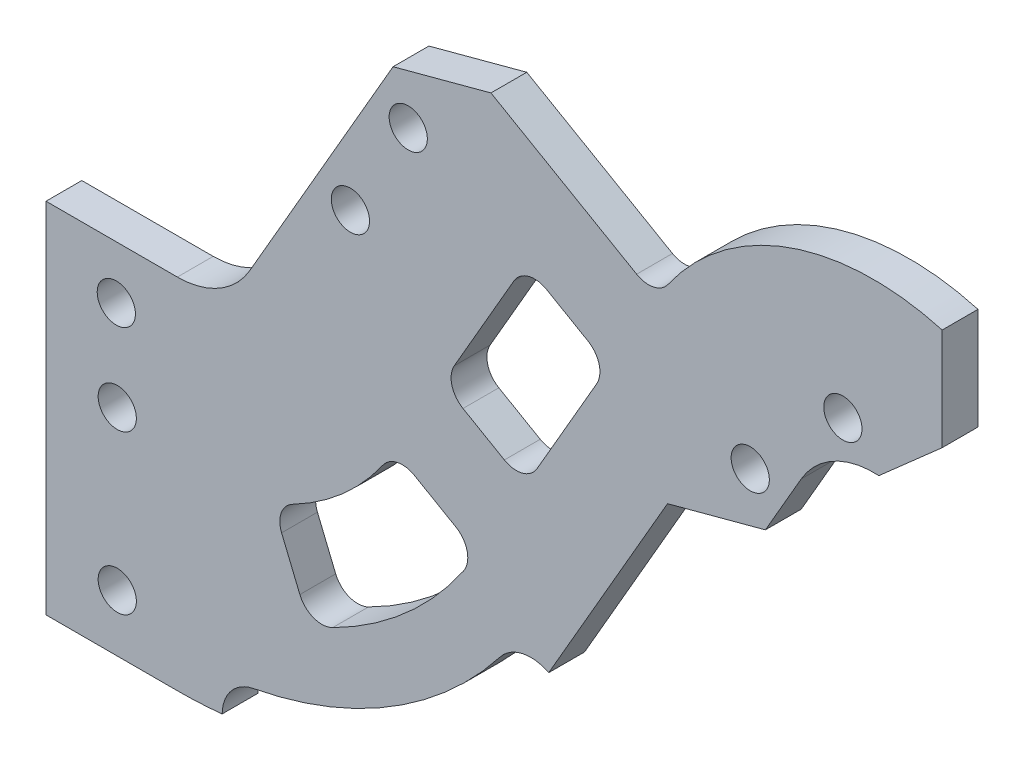
SolidWorks part; units mm, degrees
ref_plane "Front Plane" through (0, 0, 0) normal (0, 0, 1) x (1, 0, 0)
ref_plane "Top Plane" through (0, 0, 0) normal (0, 1, 0) x (1, 0, 0)
ref_plane "Right Plane" through (0, 0, 0) normal (1, 0, 0) x (0, 0, -1)
sketch "Sketch1" plane through (0, 0, 0) normal (0, 0, 1) x (1, 0, 0)
  line L0 (-45.5248, 28.6646) -> (-37.3286, 30.8608) construction
  line L1 (-53.0248, 15.6742) -> (-45.5248, 28.6646) construction
  line L2 (-45.5248, 28.6646) -> (-37.3286, 30.8608)
  line L3 (-57.5248, 7.88) -> (-45.5248, 28.6646)
  line L4 (-30.6183, -5.5166) -> (-22.544, 8.4685) construction
  line L5 (-22.544, 8.4685) -> (-14.3479, 10.6646) construction
  line L6 (-14.3479, 10.6646) -> (-11.3479, 15.8608) construction
  line L7 (-4.8483, 19.3471) -> (0.4544, 24.0249) construction
  line L8 (-32.4942, -8.7657) -> (-22.544, 8.4685)
  line L9 (-22.544, 8.4685) -> (-14.3479, 10.6646)
  line L10 (-14.3479, 10.6646) -> (-11.3479, 15.8608)
  line L11 (-4.8483, 19.3471) -> (0.4544, 24.0249)
  line L12 (0.4544, 24.0249) -> (0.4544, 32.5611)
  line L13 (-63.587, 4.38) -> (-74.587, 4.38)
  line L14 (-74.587, 4.38) -> (-74.587, -25.62)
  line L15 (-74.587, -25.62) -> (-63.587, -25.62)
  line L16 (-63.587, -1.62) -> (-63.587, -25.62) construction
  line L17 (-28.6042, 25.8237) -> (-25.1288, 23.8172) construction
  line L18 (-29.2043, 16.9326) -> (-32.6684, 18.9326) construction
  line L19 (-35.4004, 18.2005) -> (-40.4004, 9.5403) construction
  line L20 (-39.6684, 6.8082) -> (-36.2043, 4.8082) construction
  line L21 (-33.4722, 5.5403) -> (-28.4722, 14.2005) construction
  line L22 (-54.8583, -9.8051) -> (-53.3295, -13.5155) construction
  line L23 (-43.7438, -0.0764) -> (-40.2685, -2.0829) construction
  line L24 (-43.7438, -0.0764) -> (-40.2685, -2.0829)
  line L25 (-54.8583, -9.8051) -> (-53.3295, -13.5155)
  line L26 (-33.4722, 5.5403) -> (-28.4722, 14.2005)
  line L27 (-39.6684, 6.8082) -> (-36.2043, 4.8082)
  line L28 (-35.4004, 18.2005) -> (-40.4004, 9.5403)
  line L29 (-29.2043, 16.9326) -> (-32.6684, 18.9326)
  line L30 (-37.3286, 30.8608) -> (-25.1288, 23.8172)
  arc A2 (-4.8483, 19.3471) -> (-11.3479, 15.8608) centre (-5.2857, 12.3608) ccw construction
  arc A3 (-4.8483, 19.3471) -> (-11.3479, 15.8608) centre (-5.2857, 12.3608) ccw
  arc A4 (-57.5248, 7.88) -> (-63.587, 4.38) centre (-63.587, 11.38) cw
  arc A5 (-57.1936, -22.268) -> (-59.8368, -25.4294) centre (-56.587, -25.4609) ccw
  arc A6 (-32.4942, -8.7657) -> (-36.5568, -9.6541) centre (-33.9919, -11.65) ccw
  arc A7 (-57.1936, -22.268) -> (-36.5568, -9.6541) centre (-63.587, 11.38) ccw
  arc A9 (-63.587, -25.62) -> (-59.8368, -25.4294) centre (-63.587, 11.38) ccw
  arc A10 (-59.7655, -29.4415) -> (-29.1738, -10.9075) centre (-63.587, 11.38) ccw construction
  arc A11 (-63.587, -1.62) -> (-52.3286, 4.88) centre (-63.587, 11.38) ccw construction
  arc A14 (-25.1288, 23.8172) -> (-22.4903, 24.4024) centre (-24.1288, 25.5493) ccw construction
  arc A15 (13.3616, 22.0189) -> (-22.4903, 24.4024) centre (-5.2857, 12.3608) ccw construction
  arc A16 (-32.6684, 18.9326) -> (-35.4004, 18.2005) centre (-33.6684, 17.2005) ccw construction
  arc A17 (-40.4004, 9.5403) -> (-39.6684, 6.8082) centre (-38.6684, 8.5403) ccw construction
  arc A18 (-36.2043, 4.8082) -> (-33.4722, 5.5403) centre (-35.2043, 6.5403) ccw construction
  arc A19 (-28.4722, 14.2005) -> (-29.2043, 16.9326) centre (-30.2043, 15.2005) ccw construction
  arc A20 (-43.7438, -0.0764) -> (-46.3824, -0.6616) centre (-44.7438, -1.8085) ccw construction
  arc A21 (-53.9289, -7.2673) -> (-46.3824, -0.6616) centre (-63.587, 11.38) ccw construction
  arc A22 (-53.9289, -7.2673) -> (-54.8583, -9.8051) centre (-53.0091, -9.0432) ccw construction
  arc A23 (-53.3295, -13.5155) -> (-50.5835, -14.5412) centre (-51.4803, -12.7536) ccw construction
  arc A24 (-50.5835, -14.5412) -> (-39.6153, -4.9405) centre (-63.587, 11.38) ccw construction
  arc A25 (-39.6153, -4.9405) -> (-40.2685, -2.0829) centre (-41.2685, -3.8149) ccw construction
  arc A26 (-50.5835, -14.5412) -> (-39.6153, -4.9405) centre (-63.587, 11.38) ccw
  arc A27 (-53.3295, -13.5155) -> (-50.5835, -14.5412) centre (-51.4803, -12.7536) ccw
  arc A28 (-53.9289, -7.2673) -> (-54.8583, -9.8051) centre (-53.0091, -9.0432) ccw
  arc A29 (-53.9289, -7.2673) -> (-46.3824, -0.6616) centre (-63.587, 11.38) ccw
  arc A30 (-43.7438, -0.0764) -> (-46.3824, -0.6616) centre (-44.7438, -1.8085) ccw
  arc A31 (-28.4722, 14.2005) -> (-29.2043, 16.9326) centre (-30.2043, 15.2005) ccw
  arc A32 (-36.2043, 4.8082) -> (-33.4722, 5.5403) centre (-35.2043, 6.5403) ccw
  arc A33 (-40.4004, 9.5403) -> (-39.6684, 6.8082) centre (-38.6684, 8.5403) ccw
  arc A34 (-32.6684, 18.9326) -> (-35.4004, 18.2005) centre (-33.6684, 17.2005) ccw
  arc A35 (0.4544, 32.5611) -> (-22.4903, 24.4024) centre (-5.2857, 12.3608) ccw
  arc A36 (-25.1288, 23.8172) -> (-22.4903, 24.4024) centre (-24.1288, 25.5493) ccw
  arc A39 (-39.6153, -4.9405) -> (-40.2685, -2.0829) centre (-41.2685, -3.8149) ccw
  circle A40 centre (-7.8608, 22.0235) radius 1.6 construction
  circle A41 centre (-15.6175, 14.4655) radius 1.6 construction
  circle A42 centre (-44.2552, 24.8637) radius 1.6 construction
  circle A43 centre (-49.0983, 16.4751) radius 1.6 construction
  circle A44 centre (-7.8608, 22.0235) radius 1.6
  circle A45 centre (-15.6175, 14.4655) radius 1.6
  circle A46 centre (-44.2552, 24.8637) radius 1.6
  circle A47 centre (-49.0983, 16.4751) radius 1.6
  point P5 (-36.2043, 30.8608)
  dimension "D1" = 6.5
  dimension "D2" = 11
extrude "Extrude1" add sketch "Sketch1" along normal blind 3
sketch "Sketch2" plane through (0, 0, 0) normal (0, 0, -1) x (-1, 0, 0)
  circle A0 centre (68.7008, -0.06) radius 1.6
  circle A1 centre (68.6208, -7.5918) radius 1.6
  circle A2 centre (68.6208, -20.852) radius 1.6
  dimension "D1" = 3.2
extrude "Cut-Extrude1" cut sketch "Sketch2" against normal blind 10
